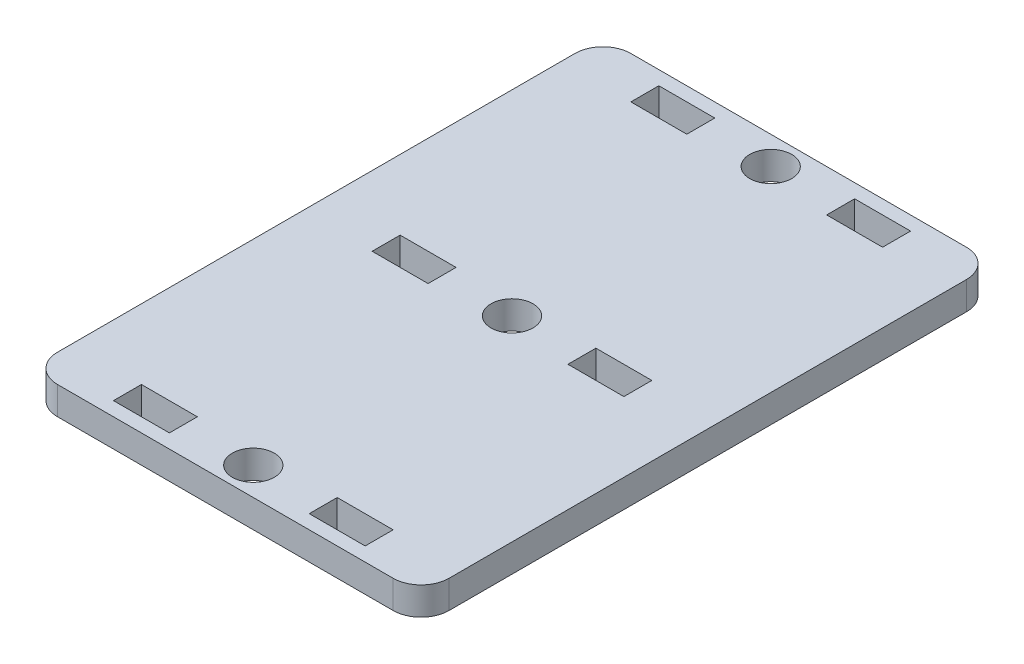
SolidWorks part; units mm, degrees
ref_plane "Front Plane" through (0, 0, 0) normal (0, 0, 1) x (1, 0, 0)
ref_plane "Top Plane" through (0, 0, 0) normal (0, 1, 0) x (1, 0, 0)
ref_plane "Right Plane" through (0, 0, 0) normal (1, 0, 0) x (0, 0, -1)
sketch "Sketch1" plane through (0, 0, 0) normal (0, 1, 0) x (1, 0, 0)
  line L0 (0, 10.25) -> (65.5, 10.25) construction
  line L1 (0, 0) -> (37.5, 0)
  line L2 (0, 0) -> (0, 20.5)
  line L3 (0, 20.5) -> (37.5, 20.5)
  line L4 (65.5, -0.75) -> (65.5, 21.25)
  line L5 (10.25, 10.25) -> (10.25, 20.5) construction
  line L8 (37.5, 0) -> (37.5, -10.25)
  line L10 (65.5, 21.25) -> (65.5, 30.75)
  line L11 (65.5, 30.75) -> (37.5, 30.75)
  line L12 (37.5, 20.5) -> (37.5, 30.75)
  line L13 (65.5, -10.25) -> (37.5, -10.25)
  line L14 (65.5, -0.75) -> (65.5, -10.25)
  circle A0 centre (10.25, 10.25) radius 2.25
  dimension "D3" = 4.5
  dimension "D4" = 20.5
  dimension "D5" = 10.25
  dimension "D6" = 55.25
  dimension "D7" = 41
  dimension "D8" = 28
extrude "Boss-Extrude1" add sketch "Sketch1" along normal blind 2
fillet "Fillet1" radius 10.25 2 edges at (0, 1, -20.5) (0, 1, 0)
fillet "Fillet2" radius 2 4 edges at (37.5, 1, -30.75) (65.5, 1, -30.75) (65.5, 1, 10.25) (37.5, 1, 10.25)
sketch "Sketch2" plane through (0, 2, 0) normal (0, 1, 0) x (1, 0, 0)
  line L0 (65.5, 10.25) -> (0, 10.25) construction
  line L1 (65.5, -8.25) -> (65.5, 28.75) construction
  line L2 (37.5, 28.75) -> (65.5, 28.75) construction
  line L3 (37.5, 28.75) -> (37.5, 20.5) construction
  line L15 (63.5, 30.75) -> (39.5, 30.75) construction
  line L17 (42.5, 27.75) -> (46.5, 27.75)
  line L18 (42.5, 27.75) -> (42.5, 29.75)
  line L19 (42.5, 29.75) -> (46.5, 29.75)
  line L20 (46.5, 27.75) -> (46.5, 29.75)
  line L21 (42.5, 27.75) -> (46.5, 29.75) construction
  line L22 (42.5, 29.75) -> (46.5, 27.75) construction
  line L23 (60.5, 27.75) -> (56.5, 27.75)
  line L24 (60.5, 27.75) -> (60.5, 29.75)
  line L25 (60.5, 29.75) -> (56.5, 29.75)
  line L26 (56.5, 27.75) -> (56.5, 29.75)
  line L27 (60.5, 27.75) -> (56.5, 29.75) construction
  line L28 (60.5, 29.75) -> (56.5, 27.75) construction
  line L37 (42.5, 9.25) -> (42.5, 11.25)
  line L38 (42.5, 9.25) -> (46.5, 9.25)
  line L39 (46.5, 9.25) -> (46.5, 11.25)
  line L40 (42.5, 11.25) -> (46.5, 11.25)
  line L41 (60.5, 9.25) -> (60.5, 11.25)
  line L42 (60.5, 9.25) -> (56.5, 9.25)
  line L43 (56.5, 9.25) -> (56.5, 11.25)
  line L44 (60.5, 11.25) -> (56.5, 11.25)
  line L53 (42.5, -9.25) -> (42.5, -7.25)
  line L54 (42.5, -9.25) -> (46.5, -9.25)
  line L55 (46.5, -9.25) -> (46.5, -7.25)
  line L56 (42.5, -7.25) -> (46.5, -7.25)
  line L57 (60.5, -9.25) -> (60.5, -7.25)
  line L58 (60.5, -9.25) -> (56.5, -9.25)
  line L59 (56.5, -9.25) -> (56.5, -7.25)
  line L60 (60.5, -7.25) -> (56.5, -7.25)
  circle A3 centre (51.5, 28.75) radius 1.5
  circle A4 centre (51.5, 10.25) radius 1.5
  circle A5 centre (51.5, -8.25) radius 1.5
  point P9 (26.5, 28.75)
  point P10 (58.5, 29.75)
  point P14 (35.5, 28.75)
  point P19 (44.5, 28.75)
  point P24 (58.5, 28.75)
  dimension "D11" = 3
  dimension "D12" = 5
  dimension "D2" = 4
  dimension "D3" = 1
  dimension "D5" = 5
  dimension "D6" = 10
  dimension "D8" = 3
extrude "Cut-Extrude1" cut sketch "Sketch2" against normal blind 2
fillet "Fillet3" radius 8 2 edges at (37.5, 1, 0) (37.5, 1, -20.5)
sketch "Sketch3" plane through (0, 2, 0) normal (0, 1, 0) x (1, 0, 0)
  line L1 (37.5, 28.75) -> (-3.343, 28.75)
  line L2 (37.5, 28.75) -> (37.5, -10.988)
  line L3 (37.5, -10.988) -> (-3.343, -10.988)
  line L4 (-3.343, 28.75) -> (-3.343, -10.988)
extrude "Cut-Extrude2" cut sketch "Sketch3" against normal blind 2
